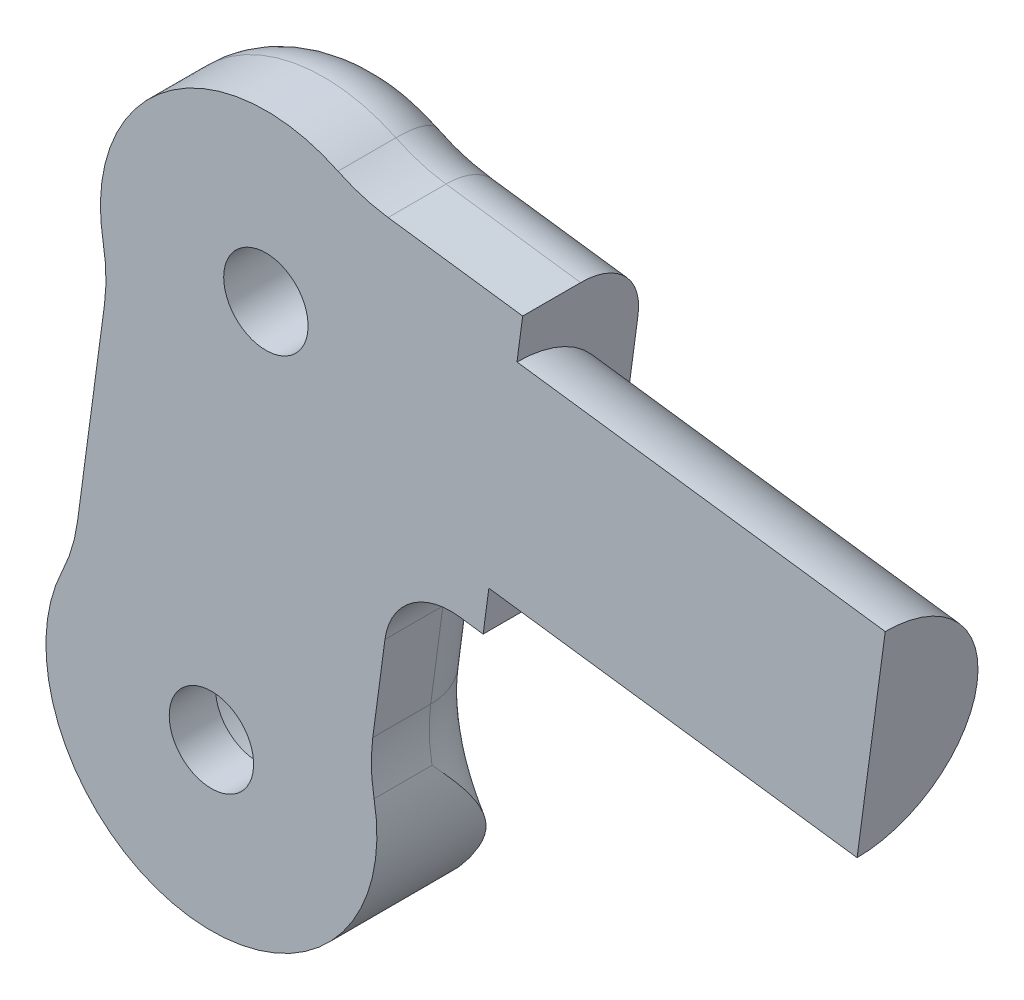
SolidWorks part; units mm, degrees
ref_plane "前视基准面" through (0, 0, 0) normal (0, 0, 1) x (1, 0, 0)
ref_plane "上视基准面" through (0, 0, 0) normal (0, 1, 0) x (1, 0, 0)
ref_plane "右视基准面" through (0, 0, 0) normal (1, 0, 0) x (0, 0, -1)
sketch "草图4" plane through (0, 0, 0) normal (0, 0, 1) x (1, 0, 0)
  arc B0 (4.3559, 9.0014) -> (-9.499, -3.1256) centre (0, 0) ccw
  arc B1 (4.3559, 9.0014) -> (7.3844, 8.0914) centre (8.7119, 18.0029) ccw
  line B2 (15.5168, 7.0022) -> (7.3844, 8.0914)
  line B3 (13.1274, -10.8385) -> (15.5168, 7.0022)
  arc B4 (11.6903, -10.646) -> (7.1947, -14.0796) centre (11.1593, -14.6106) ccw
  line B5 (11.6903, -10.646) -> (13.1274, -10.8385)
  circle B6 centre (0, 0) radius 2.55
  line B7 (6.4573, -19.5857) -> (7.1947, -14.0796)
  arc B8 (6.4573, -19.5857) -> (6.5384, -22.7469) centre (16.3688, -20.9131) ccw
  arc B9 (-12.2935, -20.2248) -> (6.5384, -22.7469) centre (-3.2921, -24.5807) ccw
  arc B10 (-3.2334, -18.081) -> (-1.6383, -18.2946) centre (-3.2921, -24.5807) ccw construction
  circle B11 centre (-3.2921, -24.5807) radius 2.55
  line B12 (-9.499, -3.1256) -> (-11.3834, -17.1963)
  arc B13 (-12.2935, -20.2248) -> (-11.3834, -17.1963) centre (-21.2949, -15.8689) ccw
  line B14 (37.423, 1.4451) -> (15.1717, 4.4252)
  line B15 (-1.6383, -18.2946) -> (-3.2334, -18.081) construction
  line B16 (13.4726, -8.2615) -> (35.7239, -11.2416)
  line B17 (35.7239, -11.2416) -> (37.423, 1.4451)
sketch_block_instance "块2-1"
sketch_block "块2"
sketch "草图5" plane through (0, 0, 0) normal (0, 0, 1) x (1, 0, 0)
  line L0 (15.5168, 7.0022) -> (7.3844, 8.0914) construction
  line L1 (13.1274, -10.8385) -> (15.5168, 7.0022) construction
  line L2 (11.6903, -10.646) -> (13.1274, -10.8385) construction
  line L3 (6.4573, -19.5857) -> (7.1947, -14.0796) construction
  line L4 (-9.499, -3.1256) -> (-11.3834, -17.1963) construction
  line L5 (15.5168, 7.0022) -> (7.3844, 8.0914)
  line L6 (13.1274, -10.8385) -> (15.5168, 7.0022)
  line L7 (11.6903, -10.646) -> (13.1274, -10.8385)
  line L8 (6.4573, -19.5857) -> (7.1947, -14.0796)
  line L9 (-9.7493, -4.995) -> (-11.3834, -17.1963)
  arc A0 (4.3559, 9.0014) -> (-9.499, -3.1256) centre (0, 0) ccw construction
  arc A1 (4.3559, 9.0014) -> (7.3844, 8.0914) centre (8.7119, 18.0029) ccw construction
  arc A2 (11.6903, -10.646) -> (7.1947, -14.0796) centre (11.1593, -14.6106) ccw construction
  circle A3 centre (0, 0) radius 2.55 construction
  arc A4 (6.4573, -19.5857) -> (6.5384, -22.7469) centre (16.3688, -20.9131) ccw construction
  arc A5 (-12.2935, -20.2248) -> (6.5384, -22.7469) centre (-3.2921, -24.5807) ccw construction
  circle A6 centre (-3.2921, -24.5807) radius 2.55 construction
  arc A7 (-12.2935, -20.2248) -> (-11.3834, -17.1963) centre (-21.2949, -15.8689) ccw construction
  arc A8 (4.3559, 9.0014) -> (-9.8304, -1.8338) centre (0, 0) ccw
  arc A9 (4.3559, 9.0014) -> (7.3844, 8.0914) centre (8.7119, 18.0029) ccw
  arc A10 (11.6903, -10.646) -> (7.1947, -14.0796) centre (11.1593, -14.6106) ccw
  circle A11 centre (0, 0) radius 2.55
  arc A12 (6.4573, -19.5857) -> (6.5384, -22.7469) centre (16.3688, -20.9131) ccw
  arc A13 (-12.2935, -20.2248) -> (6.5384, -22.7469) centre (-3.2921, -24.5807) ccw
  circle A14 centre (-3.2921, -24.5807) radius 2.55
  arc A15 (-12.2935, -20.2248) -> (-11.3834, -17.1963) centre (-21.2949, -15.8689) ccw
  arc A16 (-9.8304, -1.8338) -> (-9.7493, -4.995) centre (-19.6608, -3.6676) cw
  dimension "D1" = 10
extrude "凸台-拉伸3" add sketch "草图5" along normal blind 15
fillet "圆角4" radius 4 15 edges at (5.834, 8.4259, 0) (11.4506, 7.5468, 0) (-6.0699, 7.9471, 0) (-9.6641, -3.4112, 0) (-10.5664, -11.0957, 0) (-11.718, -18.7468, 0) (6.3721, -21.1695, 0) (6.826, -16.8327, 0) (12.4088, -10.7423, 0) (6.826, -16.8327, 15) (6.3721, -21.1695, 15) (12.4088, -10.7423, 15) (-10.5664, -11.0957, 15) (-11.718, -18.7468, 15) (11.4506, 7.5468, 15)
sketch "草图6" plane through (14.3221, -1.9181, 0) normal (0.9912, -0.1327, 0) x (0, 0, -1)
  line L0 (-15, -5) -> (-15, 5) construction
  line L1 (-11, 9) -> (-4, 9) construction
  circle A0 centre (-7.5, 0) radius 6.4
  dimension "D3" = 12.8
  dimension "D1" = 7.5
  dimension "D2" = 9
extrude "凸台-拉伸4" add sketch "草图6" along normal up to vertex (22.45 mm away)
sketch "草图7" plane through (0, 0, 15) normal (0, 0, 1) x (1, 0, 0)
  circle A0 centre (-3.2921, -24.5807) radius 6.5
extrude "切除-拉伸1" cut sketch "草图7" against normal blind 4.7
sketch "草图8" plane through (0, 0, 0) normal (0, 0, -1) x (-1, 0, 0)
  circle A0 centre (3.2921, -24.5807) radius 6.5
extrude "切除-拉伸2" cut sketch "草图8" against normal blind 4.7
sketch "草图9" plane through (36.5735, -4.8982, 0) normal (0.9912, -0.1327, 0) x (0, 0, -1)
  line L0 (-15, -28.6014) -> (-15, -34.8002) construction
  line L1 (-15, -34.8002) -> (-7.5, -34.8002)
  line L2 (-15, -34.8002) -> (-15, 15.1998)
  line L3 (-15, 15.1998) -> (-7.5, 15.1998)
  line L4 (-7.5, -34.8002) -> (-7.5, 15.1998)
  line L5 (-15, -34.8002) -> (0, -34.8002) construction
  dimension "D1" = 7.5
  dimension "D2" = 50
extrude "切除-拉伸3" cut sketch "草图9" against normal through all
sketch "草图10" plane through (0, 0, 0) normal (0, 0, -1) x (-1, 0, 0)
  line L1 (2.0207, -3.5) -> (4.0415, 0)
  line L2 (4.0415, 0) -> (2.0207, 3.5)
  line L3 (2.0207, 3.5) -> (-2.0207, 3.5)
  line L4 (-2.0207, 3.5) -> (-4.0415, 0)
  line L5 (-4.0415, 0) -> (-2.0207, -3.5)
  line L6 (-2.0207, -3.5) -> (2.0207, -3.5)
  circle A0 centre (0, 0) radius 3.5 construction
  dimension "D1" = 7
extrude "切除-拉伸4" cut sketch "草图10" against normal blind 1.5
